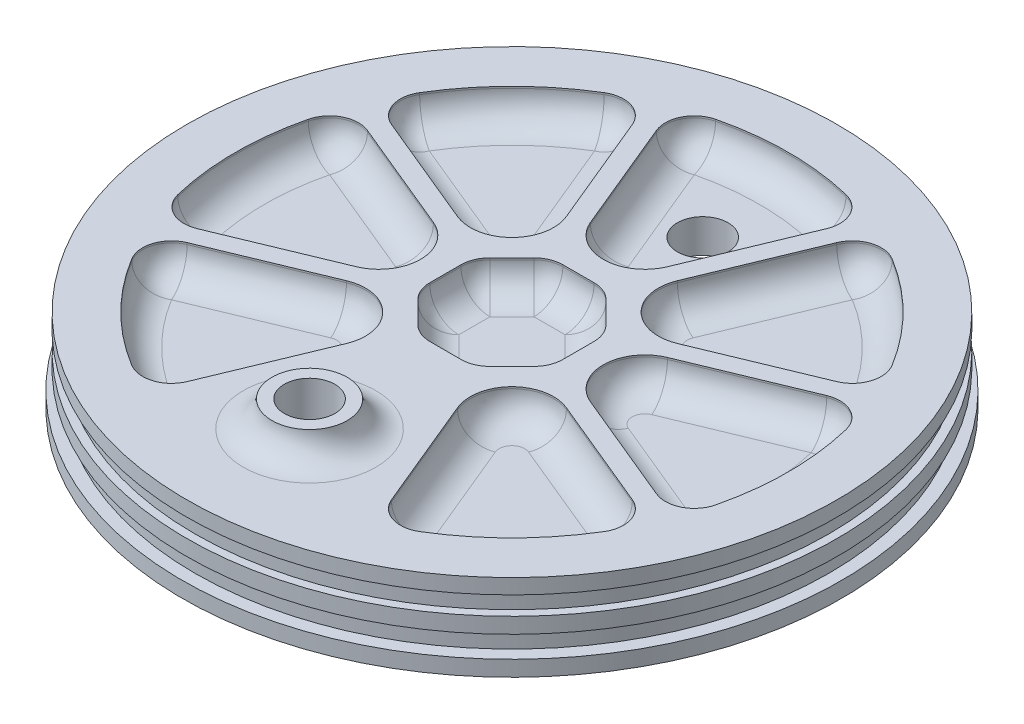
SolidWorks part; units mm, degrees
material "6061-T6 (SS)"
ref_plane "Front Plane" through (0, 0, 0) normal (0, 0, 1) x (1, 0, 0)
ref_plane "Top Plane" through (0, 0, 0) normal (0, 1, 0) x (1, 0, 0)
ref_plane "Right Plane" through (0, 0, 0) normal (1, 0, 0) x (0, 0, -1)
sketch "Sketch1" plane through (0, 0, 0) normal (0, 0, 1) x (1, 0, 0)
  line L0 (0, 48.1922) -> (0, -25.6743) construction
  line L1 (0, 0) -> (72.39, 0)
  line L2 (72.39, 0) -> (72.39, 3.429)
  line L3 (72.39, 3.429) -> (69.6468, 3.429)
  line L4 (69.6468, 3.429) -> (69.6468, 7.493)
  line L5 (69.6468, 7.493) -> (71.4248, 7.493)
  line L6 (71.4248, 7.493) -> (71.4248, 10.922)
  line L7 (71.4248, 10.922) -> (69.6468, 10.922)
  line L8 (60.7568, 18.288) -> (60.7568, 11.557)
  line L9 (60.7568, 11.557) -> (0, 11.557)
  line L10 (0, 11.557) -> (0, 0)
  line L11 (69.6468, 10.922) -> (69.6468, 14.986)
  line L12 (69.6468, 14.986) -> (71.4248, 14.986)
  line L13 (71.4248, 14.986) -> (71.4248, 18.288)
  line L14 (71.4248, 18.288) -> (60.7568, 18.288)
  dimension "D2" = 4.064
  dimension "D5" = 11.557
  dimension "D7" = 4.064
  dimension "D4" = 3.429
  dimension "D8" = 3.302
  dimension "D6" = 8.89
  dimension "D1" = 72.39
  dimension "D9" = 1.778
  dimension "D3" = 69.6468
revolve "Revolve1" add sketch "Sketch1" angle 360 about L0
sketch "Sketch6" plane through (0, 0, 0) normal (0, -1, 0) x (1, 0, 0)
  circle A0 centre (0, 0) radius 66.04
  dimension "D1" = 132.08
extrude "Boss-Extrude1" add sketch "Sketch6" along normal blind 2.54
hole_wizard "Pipe Tap Drill for 1/4 Tap - GN2" positions "Sketch2" profile "Sketch3" hole size "1/4" standard "ANSI Inch" end condition through all
sketch "Sketch2" plane through (0, 11.557, 0) normal (0, 1, 0) x (1, 0, 0)
  point P4 (0, -44.45)
  dimension "D1" = 44.45
sketch "Sketch3" plane through (0, 11.557, 44.45) normal (1, 0, 0) x (0, 0, 1)
  line L0 (0, 0) -> (0, 14.097)
  line L1 (0, 14.097) -> (5.5626, 14.097)
  line L2 (5.5626, 14.097) -> (5.5626, 0)
  line L5 (5.5626, 0) -> (0, 0)
  line L11 (0, -6.35) -> (0, 107.95) construction
  dimension "Thru Hole Dia." = 11.1252
  dimension "Thru Hole Depth" = 14.097
fillet "CNC ID Fillet" [suppressed] radius 0.4064
fillet "CNC OD Fillet" [suppressed] radius 0.127
chamfer "CNC Chamfers" [suppressed] distance 0.508 angle 65
sketch "Sketch15" plane through (0, -2.54, 0) normal (0, -1, 0) x (1, 0, 0)
  circle A0 centre (0, 44.45) radius 8.255
  circle A1 centre (0, 44.45) radius 5.5626 construction
  circle A2 centre (0, 44.45) radius 5.5626
  dimension "D1" = 16.51
extrude "Boss-Extrude2" add sketch "Sketch15" against normal blind 12.446 from surface starting at face at (0, 11.557, 50.0126)
sketch "Sketch18" plane through (0, 18.288, 0) normal (0, 1, 0) x (1, 0, 0)
  line L0 (0, 0) -> (0, 60.7568) construction
  line L1 (0, 0) -> (23.2506, 56.132) construction
  line L2 (0, 0) -> (56.132, 23.2506) construction
  line L3 (0, 0) -> (56.132, -23.2506) construction
  line L4 (0, 0) -> (23.2506, -56.132) construction
  line L5 (0, 0) -> (-23.2506, -56.132) construction
  line L6 (0, 0) -> (-56.132, -23.2506) construction
  line L7 (0, 0) -> (-56.132, 23.2506) construction
  line L8 (0, 0) -> (-23.2506, 56.132) construction
  line L9 (-8.448, 25.705) -> (-21.3733, 56.9096)
  line L10 (12.2026, 24.1498) -> (25.1279, 55.3544)
  line L11 (25.705, 8.448) -> (56.9096, 21.3733)
  line L12 (24.1498, -12.2026) -> (55.3544, -25.1279)
  line L13 (8.448, -25.705) -> (21.3733, -56.9096)
  line L14 (-12.2026, -24.1498) -> (-25.1279, -55.3544)
  line L15 (-25.705, -8.448) -> (-56.9096, -21.3733)
  line L16 (-24.1498, 12.2026) -> (-55.3544, 25.1279)
  line L17 (-12.2026, 24.1498) -> (-25.1279, 55.3544)
  line L18 (8.448, 25.705) -> (21.3733, 56.9096)
  line L19 (24.1498, 12.2026) -> (55.3544, 25.1279)
  line L20 (25.705, -8.448) -> (56.9096, -21.3733)
  line L21 (12.2026, -24.1498) -> (25.1279, -55.3544)
  line L22 (-8.448, -25.705) -> (-21.3733, -56.9096)
  line L23 (-24.1498, -12.2026) -> (-55.3544, -25.1279)
  line L24 (-25.705, 8.448) -> (-56.9096, 21.3733)
  line L25 (1.8773, 0.7776) -> (-21.3733, 56.9096) construction
  line L26 (-1.8773, 0.7776) -> (21.3733, 56.9096) construction
  line L27 (1.8773, -0.7776) -> (25.1279, 55.3544) construction
  line L28 (-0.7776, 1.8773) -> (55.3544, 25.1279) construction
  line L29 (0.7776, -1.8773) -> (56.9096, 21.3733) construction
  line L30 (0.7776, 1.8773) -> (56.9096, -21.3733) construction
  line L31 (-0.7776, -1.8773) -> (55.3544, -25.1279) construction
  line L32 (1.8773, 0.7776) -> (25.1279, -55.3544) construction
  line L33 (-1.8773, -0.7776) -> (21.3733, -56.9096) construction
  line L34 (1.8773, -0.7776) -> (-21.3733, -56.9096) construction
  line L35 (-1.8773, 0.7776) -> (-25.1279, -55.3544) construction
  line L36 (0.7776, -1.8773) -> (-55.3544, -25.1279) construction
  line L37 (-0.7776, 1.8773) -> (-56.9096, -21.3733) construction
  line L38 (-0.7776, -1.8773) -> (-56.9096, 21.3733) construction
  line L39 (0.7776, 1.8773) -> (-55.3544, 25.1279) construction
  line L40 (-1.8773, -0.7776) -> (-25.1279, 55.3544) construction
  line L42 (6.0496, 14.605) -> (-6.0496, 14.605)
  line L43 (-6.0496, 14.605) -> (-14.605, 6.0496)
  line L44 (-14.605, 6.0496) -> (-14.605, -6.0496)
  line L45 (-14.605, -6.0496) -> (-6.0496, -14.605)
  line L46 (-6.0496, -14.605) -> (6.0496, -14.605)
  line L47 (6.0496, -14.605) -> (14.605, -6.0496)
  line L48 (14.605, -6.0496) -> (14.605, 6.0496)
  line L49 (14.605, 6.0496) -> (6.0496, 14.605)
  circle A0 centre (0, 0) radius 60.7568 construction
  circle A1 centre (0, 0) radius 60.7568
  arc A2 (-8.448, 25.705) -> (8.448, 25.705) centre (0, 29.2043) ccw
  arc A3 (12.2026, 24.1498) -> (24.1498, 12.2026) centre (20.6506, 20.6506) ccw
  arc A4 (25.705, 8.448) -> (25.705, -8.448) centre (29.2043, 0) ccw
  arc A5 (24.1498, -12.2026) -> (12.2026, -24.1498) centre (20.6506, -20.6506) ccw
  arc A6 (8.448, -25.705) -> (-8.448, -25.705) centre (0, -29.2043) ccw
  arc A7 (-12.2026, -24.1498) -> (-24.1498, -12.2026) centre (-20.6506, -20.6506) ccw
  arc A8 (-25.705, -8.448) -> (-25.705, 8.448) centre (-29.2043, 0) ccw
  arc A9 (-24.1498, 12.2026) -> (-12.2026, 24.1498) centre (-20.6506, 20.6506) ccw
  circle A10 centre (0, 0) radius 14.605 construction
  circle A11 centre (0, -44.45) radius 5.5626 construction
  circle A12 centre (0, -44.45) radius 5.5626
  point P7 (0, 0)
  point P15 (0, 0)
  circle M11 centre (0, 0) radius 60.7568
  dimension "D5" = 9.144
  dimension "D6" = 29.21
  dimension "D1" = 22.5
  dimension "D3" = 2.032
  dimension "D4" = 2.032
  dimension "D2" = 8
extrude "Boss-Extrude10" add sketch "Sketch18" against normal up to surface (6.731 mm away) contours A9 L16 L24 A8 L15 L23 A7 L14 L22 A6 L13 L21 A5 L12 L20 A4 L11 L19 A3 L10 L18 A2 L9 L17 M11 | L13 A6 L22 M11 region at (0, 18.288, -18.4515) region at (-14.359, 18.288, 41.5174) up to face at (8.255, 11.557, 44.45)
fillet "Fillet14" radius 6.35 59 edges at (-14.9041, 11.557, -41.2916) (0, 11.557, -20.0603) (14.1848, 11.557, -14.1848) (18.6588, 11.557, -39.7364) (42.9615, 11.557, -42.9615) (39.7364, 11.557, -18.6588) (20.0603, 11.557, 0) (41.2916, 11.557, -14.9041) (60.7568, 11.557, 0) (41.2916, 11.557, 14.9041) (-18.6588, 11.557, -39.7364) (-14.1848, 11.557, -14.1848) (-39.7364, 11.557, -18.6588) (-42.9615, 11.557, -42.9615) (-20.0603, 11.557, 0) (-41.2916, 11.557, 14.9041) (-60.7568, 11.557, 0) (-41.2916, 11.557, -14.9041) (-14.1848, 11.557, 14.1848) (-18.6588, 11.557, 39.7364) (-42.9615, 11.557, 42.9615) (-39.7364, 11.557, 18.6588) (14.1848, 11.557, 14.1848) (39.7364, 11.557, 18.6588) (42.9615, 11.557, 42.9615) (18.6588, 11.557, 39.7364) (14.9041, 11.557, -41.2916) (0, 11.557, -60.7568) (14.605, 11.557, 0) (10.3273, 11.557, 10.3273) (0, 11.557, 14.605) (-10.3273, 11.557, 10.3273) (-14.605, 11.557, 0) (-10.3273, 11.557, -10.3273) (0, 11.557, -14.605) (10.3273, 11.557, -10.3273) (6.0496, 14.9225, 14.605) (-6.0496, 14.9225, 14.605) (-14.605, 14.9225, 6.0496) (-14.605, 14.9225, -6.0496) (-6.0496, 14.9225, -14.605) (6.0496, 14.9225, -14.605) (14.605, 14.9225, -6.0496) (14.605, 14.9225, 6.0496) (-8.255, 18.288, 44.45) (-25.1149, 14.9225, -55.3229) (-55.3229, 14.9225, -25.1149) (-56.8782, 14.9225, 21.3603) (-56.8782, 14.9225, -21.3603) (-55.3229, 14.9225, 25.1149) (-25.1149, 14.9225, 55.3229) (25.1149, 14.9225, 55.3229) (55.3229, 14.9225, 25.1149) (56.8782, 14.9225, 21.3603) (56.8782, 14.9225, -21.3603) (55.3229, 14.9225, -25.1149) (25.1149, 14.9225, -55.3229) (21.3603, 14.9225, -56.8782) (-21.3603, 14.9225, -56.8782)
sketch "Sketch19" plane through (0, 18.288, 0) normal (0, 1, 0) x (1, 0, 0)
  circle A0 centre (0, 0) radius 65.111 construction
  text T0 "IF YOURE READING THIS YOUVE MADE A SEVERE ERROR                                                                                     RELEVANT EXPERIENCE"
sketch "Sketch20" plane through (0, -2.54, 0) normal (0, -1, 0) x (1, 0, 0)
  line L3 (-8.448, 25.705) -> (-21.3733, 56.9096) construction
  line L7 (8.448, 25.705) -> (21.3733, 56.9096) construction
  line L11 (-8.448, 25.705) -> (-21.3733, 56.9096)
  line L13 (8.448, 25.705) -> (21.3733, 56.9096)
  line L16 (-50.4428, -18.6947) -> (-25.705, -8.448)
  line L17 (-25.705, 8.448) -> (-50.4428, 18.6947)
  line L18 (-50.4428, -18.6947) -> (-25.705, -8.448)
  line L19 (-25.705, 8.448) -> (-50.4428, 18.6947)
  line L31 (-12.2026, 24.1498) -> (-22.4493, 48.8876)
  line L35 (-48.8876, 22.4493) -> (-24.1498, 12.2026)
  line L39 (-12.2026, 24.1498) -> (-22.4493, 48.8876)
  line L43 (-48.8876, 22.4493) -> (-24.1498, 12.2026)
  line L47 (24.1498, 12.2026) -> (48.8876, 22.4493)
  line L52 (22.4493, 48.8876) -> (12.2026, 24.1498)
  line L53 (7.9095, -12.7451) -> (12.7451, -7.9095)
  line L54 (14.605, -3.4193) -> (14.605, 3.4193)
  line L55 (12.7451, 7.9095) -> (7.9095, 12.7451)
  line L56 (3.4193, 14.605) -> (-3.4193, 14.605)
  line L57 (-7.9095, 12.7451) -> (-12.7451, 7.9095)
  line L58 (-14.605, 3.4193) -> (-14.605, -3.4193)
  line L59 (-12.7451, -7.9095) -> (-7.9095, -12.7451)
  line L60 (-3.4193, -14.605) -> (3.4193, -14.605)
  line L61 (7.9095, -12.7451) -> (12.7451, -7.9095)
  line L62 (14.605, -3.4193) -> (14.605, 3.4193)
  line L63 (12.7451, 7.9095) -> (7.9095, 12.7451)
  line L64 (3.4193, 14.605) -> (-3.4193, 14.605)
  line L65 (-7.9095, 12.7451) -> (-12.7451, 7.9095)
  line L66 (-14.605, 3.4193) -> (-14.605, -3.4193)
  line L67 (-12.7451, -7.9095) -> (-7.9095, -12.7451)
  line L68 (-3.4193, -14.605) -> (3.4193, -14.605)
  line L69 (24.1498, 12.2026) -> (48.8876, 22.4493)
  line L70 (22.4493, 48.8876) -> (12.2026, 24.1498)
  line L71 (25.705, -8.448) -> (50.4428, -18.6947)
  line L72 (50.4428, 18.6947) -> (25.705, 8.448)
  line L73 (25.705, -8.448) -> (50.4428, -18.6947)
  line L74 (50.4428, 18.6947) -> (25.705, 8.448)
  line L75 (12.2026, -24.1498) -> (22.4493, -48.8876)
  line L76 (48.8876, -22.4493) -> (24.1498, -12.2026)
  line L77 (12.2026, -24.1498) -> (22.4493, -48.8876)
  line L78 (48.8876, -22.4493) -> (24.1498, -12.2026)
  line L79 (-8.448, -25.705) -> (-18.6947, -50.4428)
  line L80 (18.6947, -50.4428) -> (8.448, -25.705)
  line L81 (-8.448, -25.705) -> (-18.6947, -50.4428)
  line L82 (18.6947, -50.4428) -> (8.448, -25.705)
  line L83 (-24.1498, -12.2026) -> (-48.8876, -22.4493)
  line L84 (-22.4493, -48.8876) -> (-12.2026, -24.1498)
  line L85 (-24.1498, -12.2026) -> (-48.8876, -22.4493)
  line L86 (-22.4493, -48.8876) -> (-12.2026, -24.1498)
  circle A1 centre (0, 0) radius 60.7568 construction
  arc A3 (-8.448, 25.705) -> (8.448, 25.705) centre (0, 29.2043) ccw construction
  circle A8 centre (0, 0) radius 60.7568
  arc A40 (-8.448, 25.705) -> (8.448, 25.705) centre (0, 29.2043) ccw
  circle A124 centre (0, 44.45) radius 14.5732
  circle A125 centre (0, 44.45) radius 14.5732
  arc A127 (-59.0438, 14.3253) -> (-59.0438, -14.3253) centre (0, 0) ccw
  arc A128 (-59.0438, -14.3253) -> (-50.4428, -18.6947) centre (-52.8729, -12.8281) ccw
  arc A129 (-25.705, -8.448) -> (-25.705, 8.448) centre (-29.2043, 0) ccw
  arc A130 (-50.4428, 18.6947) -> (-59.0438, 14.3253) centre (-52.8729, 12.8281) ccw
  arc A131 (-59.0438, 14.3253) -> (-59.0438, -14.3253) centre (0, 0) ccw
  arc A132 (-59.0438, -14.3253) -> (-50.4428, -18.6947) centre (-52.8729, -12.8281) ccw
  arc A133 (-25.705, -8.448) -> (-25.705, 8.448) centre (-29.2043, 0) ccw
  arc A134 (-50.4428, 18.6947) -> (-59.0438, 14.3253) centre (-52.8729, 12.8281) ccw
  arc A135 (-22.4493, 48.8876) -> (-31.6208, 51.8798) centre (-28.316, 46.4576) ccw
  arc A136 (-31.6208, 51.8798) -> (-51.8798, 31.6208) centre (0, 0) ccw
  arc A137 (-51.8798, 31.6208) -> (-48.8876, 22.4493) centre (-46.4576, 28.316) ccw
  arc A138 (-24.1498, 12.2026) -> (-12.2026, 24.1498) centre (-20.6506, 20.6506) ccw
  arc A139 (12.7451, -7.9095) -> (14.605, -3.4193) centre (8.255, -3.4193) ccw
  arc A140 (14.605, 3.4193) -> (12.7451, 7.9095) centre (8.255, 3.4193) ccw
  arc A141 (7.9095, 12.7451) -> (3.4193, 14.605) centre (3.4193, 8.255) ccw
  arc A142 (-3.4193, 14.605) -> (-7.9095, 12.7451) centre (-3.4193, 8.255) ccw
  arc A143 (-12.7451, 7.9095) -> (-14.605, 3.4193) centre (-8.255, 3.4193) ccw
  arc A144 (-14.605, -3.4193) -> (-12.7451, -7.9095) centre (-8.255, -3.4193) ccw
  arc A145 (-7.9095, -12.7451) -> (-3.4193, -14.605) centre (-3.4193, -8.255) ccw
  arc A146 (3.4193, -14.605) -> (7.9095, -12.7451) centre (3.4193, -8.255) ccw
  arc A147 (12.7451, -7.9095) -> (14.605, -3.4193) centre (8.255, -3.4193) ccw
  arc A148 (14.605, 3.4193) -> (12.7451, 7.9095) centre (8.255, 3.4193) ccw
  arc A149 (7.9095, 12.7451) -> (3.4193, 14.605) centre (3.4193, 8.255) ccw
  arc A150 (-3.4193, 14.605) -> (-7.9095, 12.7451) centre (-3.4193, 8.255) ccw
  arc A151 (-12.7451, 7.9095) -> (-14.605, 3.4193) centre (-8.255, 3.4193) ccw
  arc A152 (-14.605, -3.4193) -> (-12.7451, -7.9095) centre (-8.255, -3.4193) ccw
  arc A153 (-7.9095, -12.7451) -> (-3.4193, -14.605) centre (-3.4193, -8.255) ccw
  arc A154 (3.4193, -14.605) -> (7.9095, -12.7451) centre (3.4193, -8.255) ccw
  arc A155 (-22.4493, 48.8876) -> (-31.6208, 51.8798) centre (-28.316, 46.4576) ccw
  arc A156 (-31.6208, 51.8798) -> (-51.8798, 31.6208) centre (0, 0) ccw
  arc A157 (-51.8798, 31.6208) -> (-48.8876, 22.4493) centre (-46.4576, 28.316) ccw
  arc A158 (-24.1498, 12.2026) -> (-12.2026, 24.1498) centre (-20.6506, 20.6506) ccw
  arc A159 (48.8876, 22.4493) -> (51.8798, 31.6208) centre (46.4576, 28.316) ccw
  arc A160 (51.8798, 31.6208) -> (31.6208, 51.8798) centre (0, 0) ccw
  arc A161 (31.6208, 51.8798) -> (22.4493, 48.8876) centre (28.316, 46.4576) ccw
  arc A162 (12.2026, 24.1498) -> (24.1498, 12.2026) centre (20.6506, 20.6506) ccw
  arc A163 (48.8876, 22.4493) -> (51.8798, 31.6208) centre (46.4576, 28.316) ccw
  arc A164 (51.8798, 31.6208) -> (31.6208, 51.8798) centre (0, 0) ccw
  arc A165 (31.6208, 51.8798) -> (22.4493, 48.8876) centre (28.316, 46.4576) ccw
  arc A166 (12.2026, 24.1498) -> (24.1498, 12.2026) centre (20.6506, 20.6506) ccw
  arc A167 (50.4428, -18.6947) -> (59.0438, -14.3253) centre (52.8729, -12.8281) ccw
  arc A168 (59.0438, -14.3253) -> (59.0438, 14.3253) centre (0, 0) ccw
  arc A169 (59.0438, 14.3253) -> (50.4428, 18.6947) centre (52.8729, 12.8281) ccw
  arc A170 (25.705, 8.448) -> (25.705, -8.448) centre (29.2043, 0) ccw
  arc A171 (50.4428, -18.6947) -> (59.0438, -14.3253) centre (52.8729, -12.8281) ccw
  arc A172 (59.0438, -14.3253) -> (59.0438, 14.3253) centre (0, 0) ccw
  arc A173 (59.0438, 14.3253) -> (50.4428, 18.6947) centre (52.8729, 12.8281) ccw
  arc A174 (25.705, 8.448) -> (25.705, -8.448) centre (29.2043, 0) ccw
  arc A175 (22.4493, -48.8876) -> (31.6208, -51.8798) centre (28.316, -46.4576) ccw
  arc A176 (31.6208, -51.8798) -> (51.8798, -31.6208) centre (0, 0) ccw
  arc A177 (51.8798, -31.6208) -> (48.8876, -22.4493) centre (46.4576, -28.316) ccw
  arc A178 (24.1498, -12.2026) -> (12.2026, -24.1498) centre (20.6506, -20.6506) ccw
  arc A179 (22.4493, -48.8876) -> (31.6208, -51.8798) centre (28.316, -46.4576) ccw
  arc A180 (31.6208, -51.8798) -> (51.8798, -31.6208) centre (0, 0) ccw
  arc A181 (51.8798, -31.6208) -> (48.8876, -22.4493) centre (46.4576, -28.316) ccw
  arc A182 (24.1498, -12.2026) -> (12.2026, -24.1498) centre (20.6506, -20.6506) ccw
  arc A183 (-18.6947, -50.4428) -> (-14.3253, -59.0438) centre (-12.8281, -52.8729) ccw
  arc A184 (-14.3253, -59.0438) -> (14.3253, -59.0438) centre (0, 0) ccw
  arc A185 (14.3253, -59.0438) -> (18.6947, -50.4428) centre (12.8281, -52.8729) ccw
  arc A186 (8.448, -25.705) -> (-8.448, -25.705) centre (0, -29.2043) ccw
  arc A187 (-18.6947, -50.4428) -> (-14.3253, -59.0438) centre (-12.8281, -52.8729) ccw
  arc A188 (-14.3253, -59.0438) -> (14.3253, -59.0438) centre (0, 0) ccw
  arc A189 (14.3253, -59.0438) -> (18.6947, -50.4428) centre (12.8281, -52.8729) ccw
  arc A190 (8.448, -25.705) -> (-8.448, -25.705) centre (0, -29.2043) ccw
  arc A191 (-48.8876, -22.4493) -> (-51.8798, -31.6208) centre (-46.4576, -28.316) ccw
  arc A192 (-51.8798, -31.6208) -> (-31.6208, -51.8798) centre (0, 0) ccw
  arc A193 (-31.6208, -51.8798) -> (-22.4493, -48.8876) centre (-28.316, -46.4576) ccw
  arc A194 (-12.2026, -24.1498) -> (-24.1498, -12.2026) centre (-20.6506, -20.6506) ccw
  arc A195 (-48.8876, -22.4493) -> (-51.8798, -31.6208) centre (-46.4576, -28.316) ccw
  arc A196 (-51.8798, -31.6208) -> (-31.6208, -51.8798) centre (0, 0) ccw
  arc A197 (-31.6208, -51.8798) -> (-22.4493, -48.8876) centre (-28.316, -46.4576) ccw
  arc A198 (-12.2026, -24.1498) -> (-24.1498, -12.2026) centre (-20.6506, -20.6506) ccw
  dimension "D1" = 0
  dimension "D2" = 0
  dimension "D3" = 0
  dimension "D4" = 0
  dimension "D5" = 0
  dimension "D6" = 0
  dimension "D7" = 0
  dimension "D8" = 0
  dimension "D9" = 0
extrude "Cut-Extrude1" cut sketch "Sketch20" against normal blind 6.731 contours L68 A154 L61 A147 L62 A148 L63 A149 L64 A150 L65 A151 L66 A152 L67 A153 | L43 A158 L39 A155 A8 A157 | L11 A40 L13 A8 A125 | L19 A134 A8 A132 L18 A133 | L86 A198 L85 A195 A8 A197 | L82 A190 L81 A187 A8 A189 | L78 A182 L77 A179 A8 A181 | L74 A174 L73 A171 A8 A173 | L70 A166 L69 A163 A8 A165 | A125 region at (-14.359, -2.54, 41.5174) region at (-30.7803, -2.54, 30.7803) region at (30.7803, -2.54, 30.7803) region at (-43.5299, -2.54, 0) region at (43.5299, -2.54, 0) region at (-30.7803, -2.54, -30.7803) region at (30.7803, -2.54, -30.7803) region at (0, -2.54, -43.5299) region at (0, -2.54, 0)
fillet "Fillet16" radius 6.35 64 edges at (14.9041, 4.191, 41.2916) (0, 4.191, 20.0603) (26.3465, 4.191, 52.4944) (42.9615, 4.191, 42.9615) (52.4944, 4.191, 26.3465) (36.5187, 4.191, 17.326) (14.1848, 4.191, 14.1848) (17.326, 4.191, 36.5187) (55.7489, 4.191, 18.4894) (60.7568, 4.191, 0) (55.7489, 4.191, -18.4894) (38.0739, 4.191, -13.5713) (20.0603, 4.191, 0) (38.0739, 4.191, 13.5713) (52.4944, 4.191, -26.3465) (42.9615, 4.191, -42.9615) (26.3465, 4.191, -52.4944) (17.326, 4.191, -36.5187) (14.1848, 4.191, -14.1848) (36.5187, 4.191, -17.326) (18.4894, 4.191, -55.7489) (0, 4.191, -60.7568) (-18.4894, 4.191, -55.7489) (-13.5713, 4.191, -38.0739) (0, 4.191, -20.0603) (13.5713, 4.191, -38.0739) (-26.3465, 4.191, -52.4944) (-42.9615, 4.191, -42.9615) (-52.4944, 4.191, -26.3465) (-36.5187, 4.191, -17.326) (-14.1848, 4.191, -14.1848) (-17.326, 4.191, -36.5187) (-20.0603, 4.191, 0) (-38.0739, 4.191, -13.5713) (-55.7489, 4.191, -18.4894) (-60.7568, 4.191, 0) (-55.7489, 4.191, 18.4894) (-38.0739, 4.191, 13.5713) (-52.4944, 4.191, 26.3465) (-42.9615, 4.191, 42.9615) (-26.3465, 4.191, 52.4944) (-17.326, 4.191, 36.5187) (-14.1848, 4.191, 14.1848) (-36.5187, 4.191, 17.326) (-5.8494, 4.191, -14.1216) (-10.3273, 4.191, -10.3273) (-14.1216, 4.191, -5.8494) (-14.605, 4.191, 0) (-14.1216, 4.191, 5.8494) (-10.3273, 4.191, 10.3273) (-5.8494, 4.191, 14.1216) (0, 4.191, 14.605) (5.8494, 4.191, 14.1216) (10.3273, 4.191, 10.3273) (14.1216, 4.191, 5.8494) (14.605, 4.191, 0) (14.1216, 4.191, -5.8494) (10.3273, 4.191, -10.3273) (5.8494, 4.191, -14.1216) (0, 4.191, -14.605) (21.3603, 0.8255, 56.8782) (-21.3603, 0.8255, 56.8782) (-14.9041, 4.191, 41.2916) (0, 4.191, 60.7568)
hole_wizard "Pipe Tap Drill for 1/4 Tap - Relief Valve" positions "Sketch13" profile "Sketch14" hole size "1/4" standard "ANSI Inch" end condition through all
sketch "Sketch13" plane through (0, -2.54, 0) normal (0, -1, 0) x (-1, 0, 0)
  point P4 (0, 41.91)
  dimension "D1" = 41.91
sketch "Sketch14" plane through (0, -2.54, -41.91) normal (1, 0, 0) x (0, 0, -1)
  line L0 (0, 0) -> (0, 26.543)
  line L1 (0, 26.543) -> (5.5626, 26.543)
  line L2 (5.5626, 26.543) -> (5.5626, 0)
  line L5 (5.5626, 0) -> (0, 0)
  line L11 (0, -6.35) -> (0, 107.95) construction
  dimension "Thru Hole Dia." = 11.1252
  dimension "Thru Hole Depth" = 26.543
sketch "Sketch16" plane through (0, 4.191, 0) normal (0, -1, 0) x (1, 0, 0)
  line L0 (0, 44.45) -> (0, -41.91) construction
  line L1 (-6.35, 44.45) -> (6.35, 44.45) construction
  line L2 (-9.4223, 1.27) -> (9.4223, 1.27) construction
  line L3 (25.4, -35.56) -> (-25.4, -35.56) construction
  arc A0 (-6.35, 44.45) -> (6.35, 44.45) centre (0, 44.45) ccw
  arc A1 (-6.35, -41.91) -> (6.35, -41.91) centre (0, -41.91) cw
  arc A2 (6.35, -41.91) -> (-6.35, -41.91) centre (0, -41.91) cw
  arc A3 (-6.35, 44.45) -> (6.35, 44.45) centre (0, 44.45) cw
  text T0 "GN2" font "Century Gothic" height in points 12
  text T1 "VENT\r\n" font "Century Gothic" height in points 16
  point P7 (0, 38.1)
  point P14 (0, 1.27)
  dimension "D1" = 6.35
sketch "Sketch21" plane through (0, -2.54, 0) normal (0, -1, 0) x (-1, 0, 0)
  circle A0 centre (0, 0) radius 61.5526 construction
  text T0 "DEFLAGRATION RESEARCH LABORATORY                                        THIS SIDE UP                                                   RELEVANT EXPERIENCE"
fillet "Fillet17" [suppressed] radius 3.175
equation "\"D3@Sketch1\"=5.484/2"
equation "\"D1@Sketch1\"=5.7/2"
